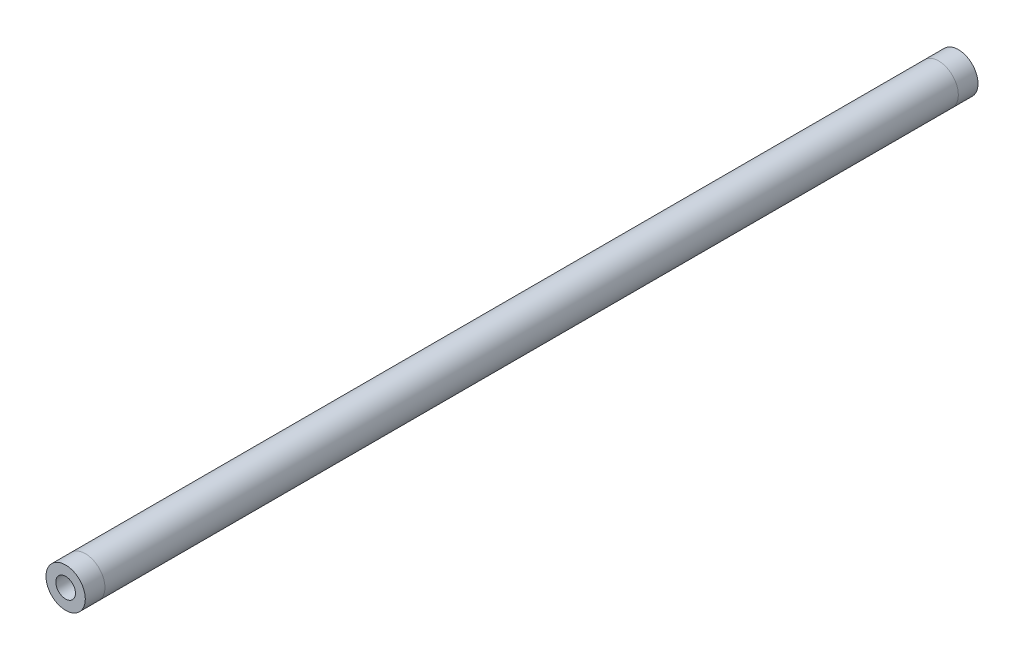
SolidWorks part; units mm, degrees
ref_plane "Front Plane" through (0, 0, 0) normal (0, 0, 1) x (1, 0, 0)
ref_plane "Top Plane" through (0, 0, 0) normal (0, 1, 0) x (1, 0, 0)
ref_plane "Right Plane" through (0, 0, 0) normal (1, 0, 0) x (0, 0, -1)
sketch "Axis" plane through (0, 0, 0) normal (1, 0, 0) x (0, 0, -1)
  line L0 (0, 0) -> (288.2624, 0) construction
  line L1 (288.2624, 0) -> (281.9124, 0)
  line L2 (288.2624, 0) -> (310.1572, 0) construction
  line L3 (0, 0) -> (-21.8948, 0) construction
  point P4 (0, 0)
  point P5 (288.2624, 0)
  point P6 (281.9124, 0)
  dimension "D1" = 6.35
  dimension "D2" = 21.8948
  dimension "D3" = 21.8948
sketch "Sketch1" plane through (0, 0, 0) normal (0, 0, 1) x (1, 0, 0)
  circle A0 centre (0, 0) radius 6.35
  circle A1 centre (0, 0) radius 4.826
  circle A2 centre (0, 0) radius 3.175
  dimension "D1" = 12.7
  dimension "D2" = 1.524
  dimension "D3" = 6.35
extrude "Threaded insert 1-1" add sketch "Sketch1" against normal blind 6.35 contours A0 A1 | A1 A2 region at (-6.1704, 0, 0) region at (-4.6895, 0, 0)
extrude "Threaded insert 1-2" add sketch "Sketch1<3>" against normal blind 9.525 from surface contours A1 A2 region at (-4.6895, 0, 0) starting at face at (6.35, 0, -6.35)
sketch "Sketch1<3>" plane through (0, 0, 0) normal (0, 0, 1) x (1, 0, 0) same geometry as "Sketch1"
extrude "Tube extrude" add sketch "Sketch1<4>" against normal up to vertex (281.9124 mm away) from surface separate body contours A0 A1 region at (-6.1704, 0, 0) up to point (0, 0, -281.9124) starting at face at (4.826, 0, -6.35)
sketch "Sketch1<4>" plane through (0, 0, 0) normal (0, 0, 1) x (1, 0, 0) same geometry as "Sketch1"
extrude "Threaded insert 2-1" add sketch "Sketch1<6>" along normal blind 9.525 from surface separate body contours A1 A2 region at (-4.6895, 0, 0) starting at face at (4.826, 0, -281.9124)
sketch "Sketch1<6>" plane through (0, 0, 0) normal (0, 0, 1) x (1, 0, 0) same geometry as "Sketch1"
extrude "Threaded insert 2-2" add sketch "Sketch1<9>" against normal blind 6.35 from surface separate body contours A1 A2 | A0 A1 region at (-6.1704, 0, 0) region at (-4.6895, 0, 0) starting at face at (4.826, 0, -281.9124)
sketch "Sketch1<9>" plane through (0, 0, 0) normal (0, 0, 1) x (1, 0, 0) same geometry as "Sketch1"
combine bodies "Combine1" operation type add bodies to combine 106 104
equation "\"Threaded insert outer thickness\"= .25"
equation "\"D1@Threaded insert 1-1\"=\"Threaded insert outer thickness\""
equation "\"D1@Threaded insert 2-2\"=\"Threaded insert outer thickness\""
equation "\"D1@Axis\" = \"Threaded insert outer thickness\""
